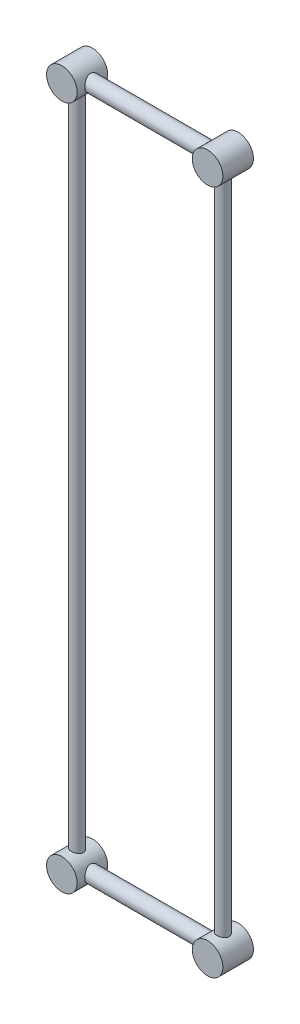
SolidWorks part; units mm, degrees
ref_plane "Front Plane" through (0, 0, 0) normal (0, 0, 1) x (1, 0, 0)
ref_plane "Top Plane" through (0, 0, 0) normal (0, 1, 0) x (1, 0, 0)
ref_plane "Right Plane" through (0, 0, 0) normal (1, 0, 0) x (0, 0, -1)
sketch "Sketch1" plane through (0, 0, 0) normal (1, 0, 0) x (0, 0, -1)
  circle A0 centre (0, 0) radius 5
  dimension "D1" = 10
extrude "Boss-Extrude1" add sketch "Sketch1" along normal blind 80
sketch "Sketch2" plane through (0, 0, 0) normal (0, 0, 1) x (1, 0, 0)
  circle A0 centre (-7.666, 0) radius 10
  point P2 (-7.666, 0)
  dimension "D1" = 20
extrude "Boss-Extrude2" add sketch "Sketch2" along normal blind 10 and the other way blind 10 separate body
sketch "Sketch3" plane through (0, 0, 0) normal (0, 1, 0) x (1, 0, 0)
  line L0 (-7.666, 10) -> (-7.666, -10) construction
  circle A0 centre (-7.666, 0) radius 3.9882
  point P2 (-7.895, 0)
extrude "Boss-Extrude3" add sketch "Sketch3" against normal blind 448
ref_plane "Plane1" through (0, -224, 0) normal (0, 1, 0) x (1, 0, 0)
mirror "Mirror1" about plane through (0, -224, 0) normal (0, 1, 0) of bodies 101 103
ref_plane "Plane2" through (40, 0, 0) normal (-1, 0, 0) x (0, 0, 1)
mirror "Mirror2" about plane through (40, 0, 0) normal (-1, 0, 0) of bodies 101 104 105 103
combine bodies "Combine1" operation type add bodies to combine 108 101 109 106 103 104 107 105
ref_axis "Axis1" through (79.3422, 0, 0) along (-1, 0, 0)
ref_axis "Axis2" through (79.3422, -448, 0) along (-1, 0, 0)
